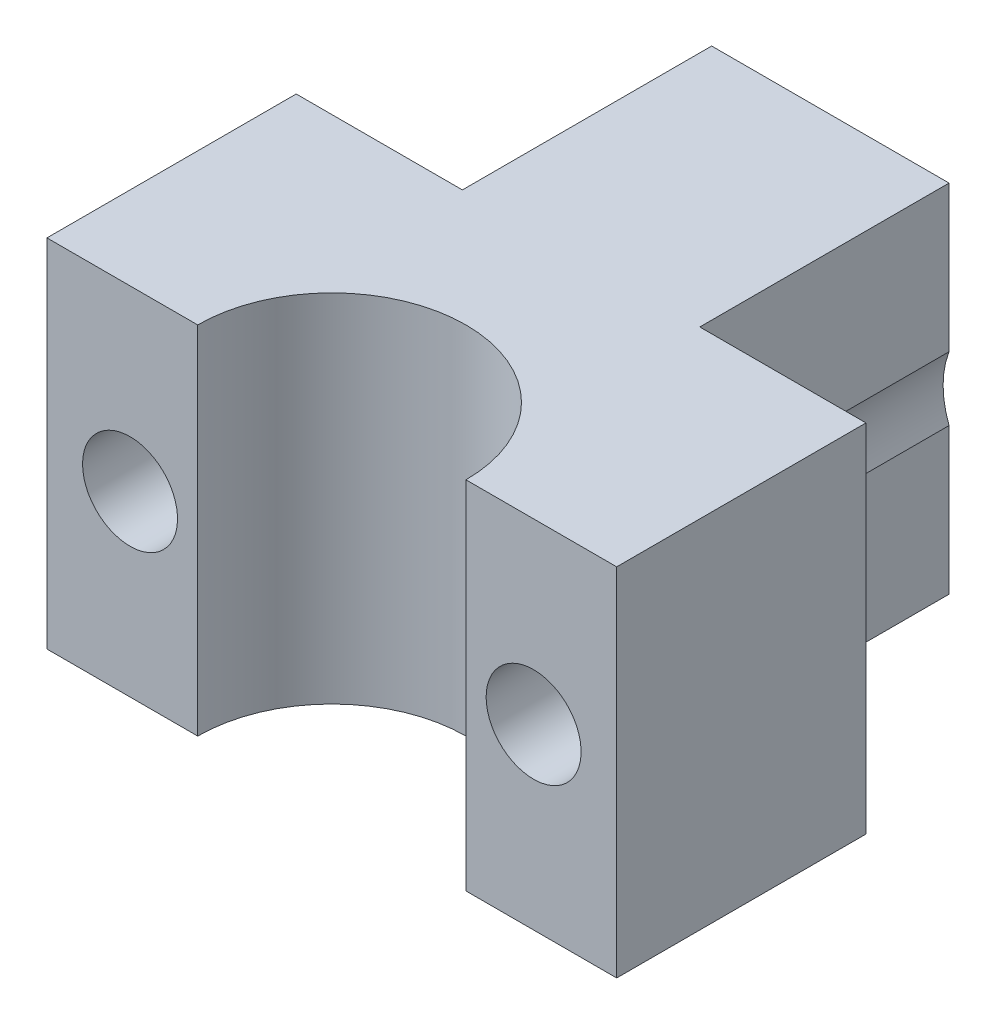
SolidWorks part; units mm, degrees
ref_plane "Спереди" through (0, 0, 0) normal (0, 0, 1) x (1, 0, 0)
ref_plane "Сверху" through (0, 0, 0) normal (0, 1, 0) x (1, 0, 0)
ref_plane "Справа" through (0, 0, 0) normal (1, 0, 0) x (0, 0, -1)
sketch "Эскиз1" plane through (0, 0, 0) normal (0, 1, 0) x (1, 0, 0)
  line L1 (-24, -10) -> (24, -10)
  line L2 (-24, -10) -> (-24, 10)
  line L3 (-24, 10) -> (24, 10)
  line L4 (24, -10) -> (24, 10)
  line L5 (-24, -10) -> (24, 10) construction
  line L6 (-24, 10) -> (24, -10) construction
  point P0 (0, 0)
  dimension "D1" = 48
  dimension "D2" = 20
extrude "Бобышка-Вытянуть1" add sketch "Эскиз1" along normal blind 30
sketch "Эскиз2" plane through (0, 0, 10) normal (0, 0, 1) x (1, 0, 0)
  line L0 (-7, 30) -> (-7, 0)
  line L1 (-24, 30) -> (24, 30) construction
  line L2 (-24, 0) -> (24, 0) construction
  line L3 (-7, 0) -> (7, 0)
  line L4 (7, 0) -> (7, 30)
  line L5 (7, 30) -> (-7, 30)
  dimension "D1" = 17
  dimension "D2" = 14
extrude "Вырез-Вытянуть1" cut sketch "Эскиз2" against normal blind 7
sketch "Эскиз7" plane through (24, 0, 0) normal (1, 0, 0) x (0, 0, -1)
  line L1 (32, 30) -> (32, 0)
  line L2 (32, 0) -> (10, 0)
  line L3 (-10, 0) -> (10, 0)
  line L4 (10, 0) -> (10.066, 0.2736)
  line L5 (10, 30) -> (32, 30)
  line L8 (10, 0) -> (10, 30)
  dimension "D3" = 22
extrude "Бобышка-Вытянуть2" add sketch "Эскиз7" against normal blind 48
sketch "Эскиз8" plane through (24, 0, 0) normal (1, 0, 0) x (0, 0, -1)
  line L0 (11, 0) -> (11, 30)
  line L1 (-10, 30) -> (32, 30) construction
  line L2 (11, 30) -> (32, 30)
  line L3 (11, 0) -> (32, 0)
  line L4 (32, 0) -> (32, 30)
  line L5 (-10, 0) -> (32, 0) construction
  point P16 (11, 0)
extrude "Вырез-Вытянуть2" cut sketch "Эскиз8" against normal blind 14
sketch "Эскиз9" plane through (-24, 0, 0) normal (-1, 0, 0) x (0, 0, 1)
  line L0 (-11, 0) -> (-11, 30)
  line L1 (-32, 30) -> (10, 30) construction
  line L2 (-11, 30) -> (-32, 30)
  line L3 (-32, 0) -> (10, 0) construction
  line L4 (-11, 0) -> (-32, 0)
  line L5 (-32, 0) -> (-32, 30)
  point P15 (-11, 0)
extrude "Вырез-Вытянуть3" cut sketch "Эскиз9" against normal blind 14
sketch "Эскиз11" plane through (-10, 0, 0) normal (-1, 0, 0) x (0, 0, 1)
  line L0 (-32, 30) -> (-11, 0) construction
  line L2 (-32, 0) -> (-11, 0) construction
  line L3 (-16.4, 4.9) -> (-16.4, 25.1)
  line L6 (-16.4, 4.9) -> (-26.6, 4.9)
  line L7 (-16.4, 25.1) -> (-26.6, 25.1)
  line L8 (-26.6, 4.9) -> (-26.6, 25.1)
  line L9 (-16.4, 4.9) -> (-26.6, 25.1) construction
  line L10 (-16.4, 25.1) -> (-26.6, 4.9) construction
  point P7 (-21.5, 15)
  point P8 (-21.5, 15)
  dimension "D1" = 20.2
  dimension "D2" = 10.2
extrude "Вырез-Вытянуть4" cut sketch "Эскиз11" against normal through all
sketch "Эскиз13" plane through (0, 0, -11) normal (0, 0, -1) x (-1, 0, 0)
  line L0 (24, 15) -> (10, 15) construction
  line L1 (24, 0) -> (24, 30) construction
  line L2 (10, 0) -> (10, 30) construction
  circle A0 centre (17, 15) radius 4
extrude "Вырез-Вытянуть5" cut sketch "Эскиз13" against normal through all
sketch "Эскиз14" plane through (0, 0, -11) normal (0, 0, -1) x (-1, 0, 0)
  line L0 (-24, 15) -> (-10, 15) construction
  line L1 (-24, 30) -> (-24, 0) construction
  line L2 (-10, 30) -> (-10, 0) construction
  circle A0 centre (-17, 15) radius 4
extrude "Вырез-Вытянуть6" cut sketch "Эскиз14" against normal through all
fillet "Скругление1" radius 7 2 edges at (-7, 15, 3) (7, 15, 3)
sketch "Sketch1" plane through (10, 0, 0) normal (1, 0, 0) x (0, 0, -1)
  line L0 (16.4, 25.1) -> (26.6, 4.9) construction
  line L2 (26.6, 4.9) -> (16.4, 4.9)
  line L3 (26.6, 4.9) -> (26.6, 25.1)
  line L4 (26.6, 25.1) -> (16.4, 25.1)
  line L5 (16.4, 4.9) -> (16.4, 25.1)
  line L6 (26.6, 4.9) -> (16.4, 25.1) construction
  line L7 (26.6, 25.1) -> (16.4, 4.9) construction
  point P4 (21.5, 15)
extrude "Boss-Extrude1" add sketch "Sketch1" against normal blind 4
sketch "Эскиз20" plane through (0, 0, -11) normal (0, 0, -1) x (-1, 0, 0)
  circle A0 centre (-17, 15) radius 7.5
  circle A1 centre (17, 15) radius 7.5
  dimension "D1" = 15
extrude "Вырез-Вытянуть8" cut sketch "Эскиз20" along normal through all
sketch "Sketch2" plane through (0, 30, 0) normal (0, 1, 0) x (1, 0, 0)
  line L0 (-7, -10) -> (7, -10) construction
  circle A0 centre (0, -10) radius 11.3
  dimension "D1" = 22.6
extrude "Cut-Extrude1" cut sketch "Sketch2" against normal through all
